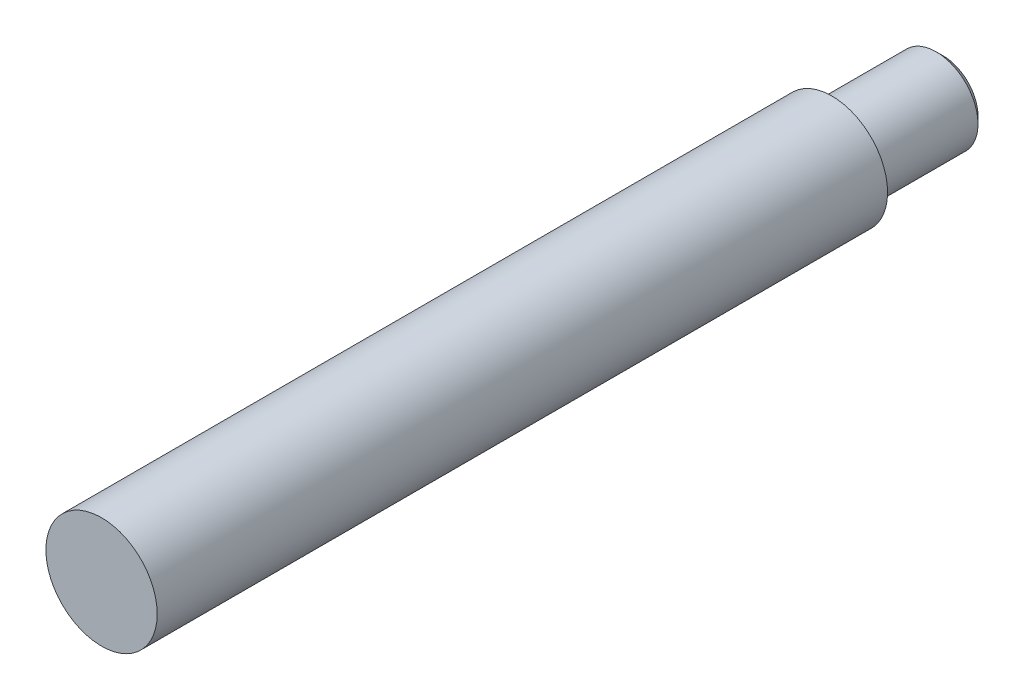
SolidWorks part; units mm, degrees
ref_plane "Front" through (0, 0, 0) normal (0, 0, 1) x (1, 0, 0)
ref_plane "Top" through (0, 0, 0) normal (0, 1, 0) x (1, 0, 0)
ref_plane "Right" through (0, 0, 0) normal (1, 0, 0) x (0, 0, -1)
sketch "Esquisse1" plane through (0, 0, 0) normal (0, 0, 1) x (1, 0, 0)
  circle A0 centre (0, 0) radius 3
  dimension "D1" = 6
extrude "Boss.-Extru.1" add sketch "Esquisse1" along normal blind 8
chamfer "Chanfrein1" distance 0.5 angle 45 1 edges at (3, 0, 0)
sketch "Esquisse2" plane through (0, 0, 8) normal (0, 0, 1) x (1, 0, 0)
  circle A0 centre (0, 0) radius 4
  dimension "D1" = 8
extrude "Boss.-Extru.2" add sketch "Esquisse2" along normal blind 52.5
